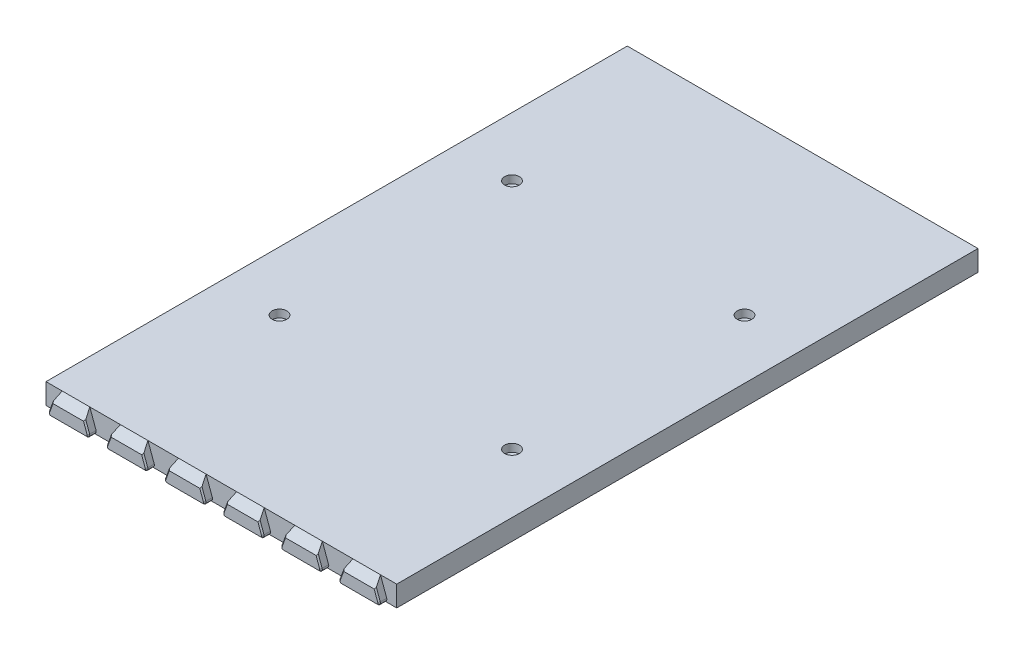
SolidWorks part; units mm, degrees
ref_plane "Front Plane" through (0, 0, 0) normal (0, 0, 1) x (1, 0, 0)
ref_plane "Top Plane" through (0, 0, 0) normal (0, 1, 0) x (1, 0, 0)
ref_plane "Right Plane" through (0, 0, 0) normal (1, 0, 0) x (0, 0, -1)
sketch "Sketch1" plane through (0, 0, 0) normal (0, 0, 1) x (1, 0, 0)
  line L0 (0, 0) -> (0, 8) construction
  line L1 (-67.875, 0) -> (0, 0) construction
  line L2 (-67.875, 0) -> (-67.875, 8)
  line L3 (-67.875, 8) -> (67.875, 8)
  line L5 (-67.875, 0) -> (-65.875, 0)
  line L6 (-65.875, 0) -> (-65.875, 6)
  line L7 (-65.875, 6) -> (65.875, 6)
  line L9 (65.875, 0) -> (65.875, 6)
  line L10 (67.875, 0) -> (65.875, 0)
  line L11 (67.875, 0) -> (67.875, 8)
  point P8 (0, 6)
  dimension "D2" = 6
  dimension "D1" = 67.875
  dimension "D3" = 2
  dimension "D4" = 2
extrude "Boss-Extrude1" add sketch "Sketch1" against normal blind 112.5
sketch "Sketch7" plane through (0, 0, 0) normal (0, 0, 1) x (1, 0, 0)
  line L2 (-65.875, 0) -> (65.875, 0)
  line L13 (-65.875, 0) -> (-65.875, 6)
  line L15 (-65.875, 6) -> (65.875, 6)
  line L16 (65.875, 0) -> (65.875, 6)
  line M3 (-65.875, 0) -> (-65.875, 6)
  line M4 (-65.875, 6) -> (65.875, 6)
  line M5 (65.875, 6) -> (65.875, 0)
extrude "Boss-Extrude7" add sketch "Sketch7" against normal blind 1 contours M4 M3 | M5 region at (0, 3, 0)
sketch "Sketch2" plane through (0, 0, 0) normal (0, 0, 1) x (1, 0, 0)
  line L14 (50.9118, 8) -> (48, 0)
  line L15 (67.875, 8) -> (-67.875, 8) construction
  line L16 (-67.875, 0) -> (67.875, 0) construction
  line L17 (48, 0) -> (64.5, 0)
  line L18 (50.9118, 8) -> (61.5882, 8)
  line L19 (-67.875, 0) -> (67.875, 0) construction
  line L21 (61.5882, 8) -> (64.5, 0)
  line L24 (45, 0) -> (45, 8) construction
  line L27 (28.4118, 8) -> (25.5, 0)
  line L28 (28.4118, 8) -> (39.0882, 8)
  line L29 (25.5, 0) -> (42, 0)
  line L30 (39.0882, 8) -> (42, 0)
  line L31 (5.9118, 8) -> (3, 0)
  line L32 (5.9118, 8) -> (16.5882, 8)
  line L33 (3, 0) -> (19.5, 0)
  line L34 (16.5882, 8) -> (19.5, 0)
  line L35 (-16.5882, 8) -> (-19.5, 0)
  line L36 (-16.5882, 8) -> (-5.9118, 8)
  line L37 (-19.5, 0) -> (-3, 0)
  line L38 (-5.9118, 8) -> (-3, 0)
  line L39 (50.9118, 8) -> (28.4118, 8) construction
  line L40 (67.5, 8) -> (67.5, 0) construction
  line L41 (67.875, 0) -> (67.875, 8) construction
  line L42 (-67.5, 8) -> (-67.5, 0) construction
  line L43 (-67.875, 8) -> (-67.875, 0) construction
  line L44 (-39.0882, 8) -> (-42, 0)
  line L45 (-39.0882, 8) -> (-28.4118, 8)
  line L46 (-42, 0) -> (-25.5, 0)
  line L47 (-28.4118, 8) -> (-25.5, 0)
  line L48 (-61.5882, 8) -> (-64.5, 0)
  line L49 (-61.5882, 8) -> (-50.9118, 8)
  line L50 (-64.5, 0) -> (-48, 0)
  line L51 (-50.9118, 8) -> (-48, 0)
  point P22 (56.25, 8)
  point P23 (33.75, 8)
  dimension "D1" = 70
  dimension "D2" = 0.375
  dimension "D3" = 3
  dimension "D4" = 3
  dimension "D5" = 70
  dimension "D7" = 22.5
  dimension "D8" = 22.5
  dimension "D9" = 0.375
  dimension "D10" = 48
  dimension "D11" = 8
  dimension "D6" = 6
extrude "Boss-Extrude4" add sketch "Sketch2" along normal blind 3
sketch "Sketch8" plane through (0, 0, 0) normal (0, -1, 0) x (1, 0, 0)
  line L0 (-67.875, -22.5) -> (67.875, -22.5) construction
  line L1 (-66.35, -20.2583) -> (-62.65, -21.605)
  line L2 (67.875, -112.5) -> (67.875, 0) construction
  line L3 (-67.875, 0) -> (-64.5, 0) construction
  line L4 (-66.5, -24.9559) -> (-66.5, -20.0441) construction
  line L5 (-66.5, -20.0441) -> (-62.5, -21.5) construction
  line L6 (-62.5, -21.5) -> (-62.5, -23.5) construction
  line L7 (-66.5, -112.5) -> (-66.5, -110.0441) construction
  line L8 (-66.5, -110.0441) -> (-62.5, -111.5) construction
  line L9 (-62.5, -111.5) -> (-62.5, -112.5) construction
  line L10 (-65.875, -112.5) -> (65.875, -112.5) construction
  line L11 (-62.5, -112.5) -> (-66.5, -112.5) construction
  line L12 (-66.5, -24.9559) -> (-62.5, -23.5) construction
  line L13 (0, -112.5) -> (0, 0) construction
  line L22 (-62.65, -21.605) -> (-62.65, -23.395)
  line L23 (-67.875, -112.5) -> (-67.875, 0) construction
  line L28 (-67.875, -112.5) -> (-65.875, -112.5) construction
  line L33 (-66.35, -24.7417) -> (-62.65, -23.395)
  line L34 (-66.35, -24.7417) -> (-66.35, -20.2583)
  line L35 (-66.35, -110.2583) -> (-62.65, -111.605)
  line L36 (-62.65, -111.605) -> (-62.65, -112.35)
  line L37 (-62.65, -112.35) -> (-66.35, -112.35) construction
  line L38 (-66.35, -112.35) -> (-66.35, -110.2583)
  line L39 (-66.35, -112.35) -> (-66.35, -112.5)
  line L40 (-66.35, -112.5) -> (-62.65, -112.5)
  line L41 (-62.65, -112.5) -> (-62.65, -112.35)
  line L42 (66.35, -24.7417) -> (66.35, -20.2583)
  line L43 (66.35, -24.7417) -> (62.65, -23.395)
  line L44 (62.65, -21.605) -> (62.65, -23.395)
  line L45 (66.35, -20.2583) -> (62.65, -21.605)
  line L46 (66.35, -112.5) -> (62.65, -112.5)
  line L47 (66.35, -112.35) -> (66.35, -112.5)
  line L48 (66.35, -112.35) -> (66.35, -110.2583)
  line L49 (66.35, -110.2583) -> (62.65, -111.605)
  line L50 (62.65, -111.605) -> (62.65, -112.35)
  line L51 (62.65, -112.5) -> (62.65, -112.35)
  point P19 (-62.5, -22.5)
  dimension "D1" = 22.5
  dimension "D2" = 0.15
  dimension "D3" = 70
  dimension "D4" = 4
  dimension "D5" = 1.375
  dimension "D6" = 4
  dimension "D7" = 70
  dimension "D8" = 1
  dimension "D9" = 1
  dimension "D10" = 0.15
extrude "Boss-Extrude8" add sketch "Sketch8" against normal up to next and the other way blind 2
chamfer "Chamfer4" distance 0.5 angle 45 14 edges at (62.65, -2, -22.5) (64.5, -2, -20.9317) (66.35, -2, -22.5) (64.5, -2, -24.0683) (-64.5, -2, -20.9317) (-62.65, -2, -22.5) (-64.5, -2, -24.0683) (-66.35, -2, -22.5) (-62.65, -2, -112.0525) (-64.5, -2, -110.9317) (-66.35, -2, -111.3792) (66.35, -2, -111.3792) (64.5, -2, -110.9317) (62.65, -2, -112.0525)
fillet "Fillet4" radius 1 12 edges at (64.5, 0, 1.5) (48, 0, 1.5) (42, 0, 1.5) (25.5, 0, 1.5) (19.5, 0, 1.5) (3, 0, 1.5) (-3, 0, 1.5) (-19.5, 0, 1.5) (-25.5, 0, 1.5) (-42, 0, 1.5) (-48, 0, 1.5) (-64.5, 0, 1.5)
chamfer "Chamfer6" distance 0.5 angle 45 30 edges at (49.7001, 4.671, 3) (62.7999, 4.671, 3) (56.25, 0, 3) (-17.7999, 4.671, 3) (-11.25, 0, 3) (-4.7001, 4.671, 3) (4.7001, 4.671, 3) (11.25, 0, 3) (17.7999, 4.671, 3) (27.2001, 4.671, 3) (40.2999, 4.671, 3) (33.75, 0, 3) (-40.2999, 4.671, 3) (-33.75, 0, 3) (-27.2001, 4.671, 3) (-49.7001, 4.671, 3) (-56.25, 0, 3) (-62.7999, 4.671, 3) (-48.609, 0.4264, 3) (-63.891, 0.4264, 3) (-41.391, 0.4264, 3) (-26.109, 0.4264, 3) (-18.891, 0.4264, 3) (-3.609, 0.4264, 3) (3.609, 0.4264, 3) (18.891, 0.4264, 3) (26.109, 0.4264, 3) (41.391, 0.4264, 3) (48.609, 0.4264, 3) (63.891, 0.4264, 3)
fillet "Fillet2" radius 2 23 edges at (0, 6, -1) (-65.875, 3, -1) (65.875, 6, -10.7156) (65.875, 3, -1) (-65.875, 6, -10.7156) (62.65, 6, -112.0525) (64.2625, 6, -111.0181) (65.875, 3, -110.4312) (64.2625, 6, -21.0181) (62.65, 6, -22.5) (64.2625, 6, -23.9819) (65.875, 6, -67.5) (65.875, 3, -24.5688) (65.875, 3, -20.4312) (-62.65, 6, -112.0525) (-64.2625, 6, -111.0181) (-65.875, 3, -110.4312) (-65.875, 3, -20.4312) (-62.65, 6, -22.5) (-64.2625, 6, -21.0181) (-64.2625, 6, -23.9819) (-65.875, 3, -24.5688) (-65.875, 6, -67.5)
mirror "Mirror2" about plane through (0, 0, -112.5) normal (0, 0, 1) of "Fillet4", "Boss-Extrude1", "Boss-Extrude7", "Boss-Extrude4", "Boss-Extrude8", "Chamfer4", "Fillet2", "Chamfer6"
sketch "Sketch9" plane through (0, 0, 0) normal (0, 1, 0) x (1, 0, 0)
  line L16 (0, 112.5) -> (0, 0) construction
  line L17 (-67.875, 112.5) -> (67.875, 112.5) construction
  line L20 (67.875, 225) -> (67.875, 0) construction
  circle A0 centre (-45, 67.5) radius 5
  circle A4 centre (45, 67.5) radius 5
  circle A5 centre (45, 157.5) radius 5
  circle A6 centre (-45, 157.5) radius 5
  point P23 (0, 112.5)
  point P24 (0, 112.5)
  dimension "D3" = 10
  dimension "D1" = 45
  dimension "D2" = 45
extrude "Boss-Extrude9" add sketch "Sketch9" along normal up to next
fillet "Fillet3" radius 3 4 edges at (-45, 6, -72.5) (-45, 6, -162.5) (45, 6, -162.5) (45, 6, -72.5)
sketch "Sketch10" plane through (0, 0, 0) normal (0, 1, 0) x (1, 0, 0)
  circle A0 centre (-45, 157.5) radius 1.85
  circle A1 centre (-45, 67.5) radius 1.85
  circle A2 centre (45, 67.5) radius 1.85
  circle A3 centre (45, 157.5) radius 1.85
  dimension "D1" = 3.7
extrude "Cut-Extrude2" cut sketch "Sketch10" along normal through all
sketch "Sketch11" plane through (0, 8, 0) normal (0, 1, 0) x (1, 0, 0)
  circle A0 centre (-45, 157.5) radius 2.85
  circle A1 centre (45, 157.5) radius 2.85
  circle A2 centre (45, 67.5) radius 2.85
  circle A3 centre (-45, 67.5) radius 2.85
  dimension "D1" = 5.7
extrude "Cut-Extrude3" cut sketch "Sketch11" against normal blind 3
chamfer "Chamfer7" distance 1 angle 45 4 edges at (45, 5, -155.65) (-45, 5, -155.65) (45, 5, -65.65) (-45, 5, -65.65)
sketch "Sketch12" plane through (0, 0, 0) normal (1, 0, 0) x (0, 0, -1)
  line L0 (0, 8) -> (-3, 5)
  line L1 (-3, 1.171) -> (-3, 8) construction
  line L2 (-3, 5) -> (-3, 8)
  line L3 (-3, 8) -> (0, 8)
  line L4 (112.5, 8) -> (112.5, 0) construction
  line L5 (225, 8) -> (0, 8) construction
  line L6 (225, 0) -> (0, 0) construction
  line L7 (228, 8) -> (225, 8)
  line L8 (228, 5) -> (228, 8)
  line L9 (225, 8) -> (228, 5)
  dimension "D1" = 45
  dimension "D2" = 3
extrude "Cut-Extrude4" cut sketch "Sketch12" against normal through all both and the other way through all
